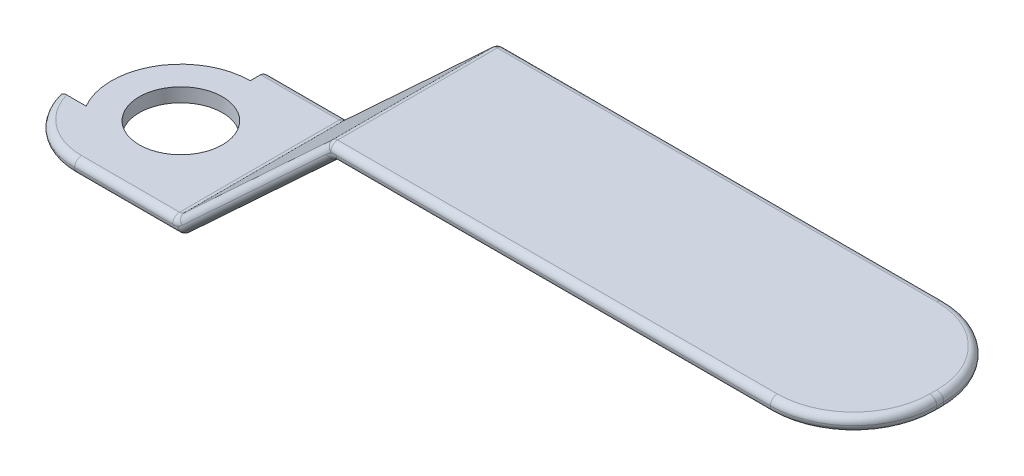
SolidWorks part; units mm, degrees
ref_plane "Front Plane" through (0, 0, 0) normal (0, 0, 1) x (1, 0, 0)
ref_plane "Top Plane" through (0, 0, 0) normal (0, 1, 0) x (1, 0, 0)
ref_plane "Right Plane" through (0, 0, 0) normal (1, 0, 0) x (0, 0, -1)
sketch "Sketch1" plane through (0, 0, 0) normal (0, 0, 1) x (1, 0, 0)
  line L0 (0, 0) -> (25, 0)
  line L1 (25, 0) -> (47, 20.3961)
  line L2 (47, 20.3961) -> (122, 20.3961)
  dimension "D1" = 25
  dimension "D2" = 30
  dimension "D3" = 75
  dimension "D4" = 22
extrude "Extrude-Thin1" add sketch "Sketch1" against normal blind 25 thin thin type one direction reverse wall 2
sketch "Sketch2" plane through (0, 2, 0) normal (0, 1, 0) x (1, 0, 0)
  line L0 (0, 25) -> (24.2155, 25) construction
  line L1 (0, 25) -> (0, 0) construction
  line L2 (0, 0) -> (0, 7.5)
  line L4 (0, 25) -> (0, 0)
  line L5 (0, 25) -> (24.2155, 25)
  line L7 (0, 7.5) -> (3.8397, 7.5)
  line L8 (12.5, 22.5) -> (12.5, 25)
  circle A0 centre (12.5, 12.5) radius 6.0005
  arc A4 (12.5, 22.5) -> (3.8397, 7.5) centre (12.5, 12.5) ccw
  line M8 (0, 25) -> (0, 0)
  dimension "D1" = 12.001
  dimension "D2" = 12.5
  dimension "D3" = 12.5
  dimension "D4" = 20
  dimension "D6" = 7.5
extrude "Cut-Extrude1" cut sketch "Sketch2" against normal through all contours A4 L8 L5 L7 M8 | A0 region at (3.7893, 2, -19.0361) region at (12.5, 2, -12.5)
fillet "Fillet1" radius 10 1 edges at (0, 1, 0)
fillet "Fillet2" radius 12 2 edges at (122, 21.3961, 0) (122, 21.3961, -25)
fillet "Fillet3" radius 1 25 edges at (3.5587, 0, -2.0943) (3.5587, 2, -2.0943) (118.4853, 22.3961, -21.4853) (122, 22.3961, -12.5) (118.4853, 22.3961, -3.5147) (118.4853, 20.3961, -21.4853) (122, 20.3961, -12.5) (118.4853, 20.3961, -3.5147) (35.2155, 12.198, -25) (18.3578, 2, -25) (18.75, 0, -25) (36, 10.198, -25) (78.5, 20.3961, -25) (78.1078, 22.3961, -25) (36, 10.198, 0) (17.3412, 0, 0) (16.949, 2, 0) (35.2155, 12.198, 0) (78.1078, 22.3961, 0) (78.5, 20.3961, 0) (47, 20.3961, -12.5) (25, 0, -12.5) (46.2155, 22.3961, -12.5) (24.2155, 2, -12.5) (12.5, 1, -25)
